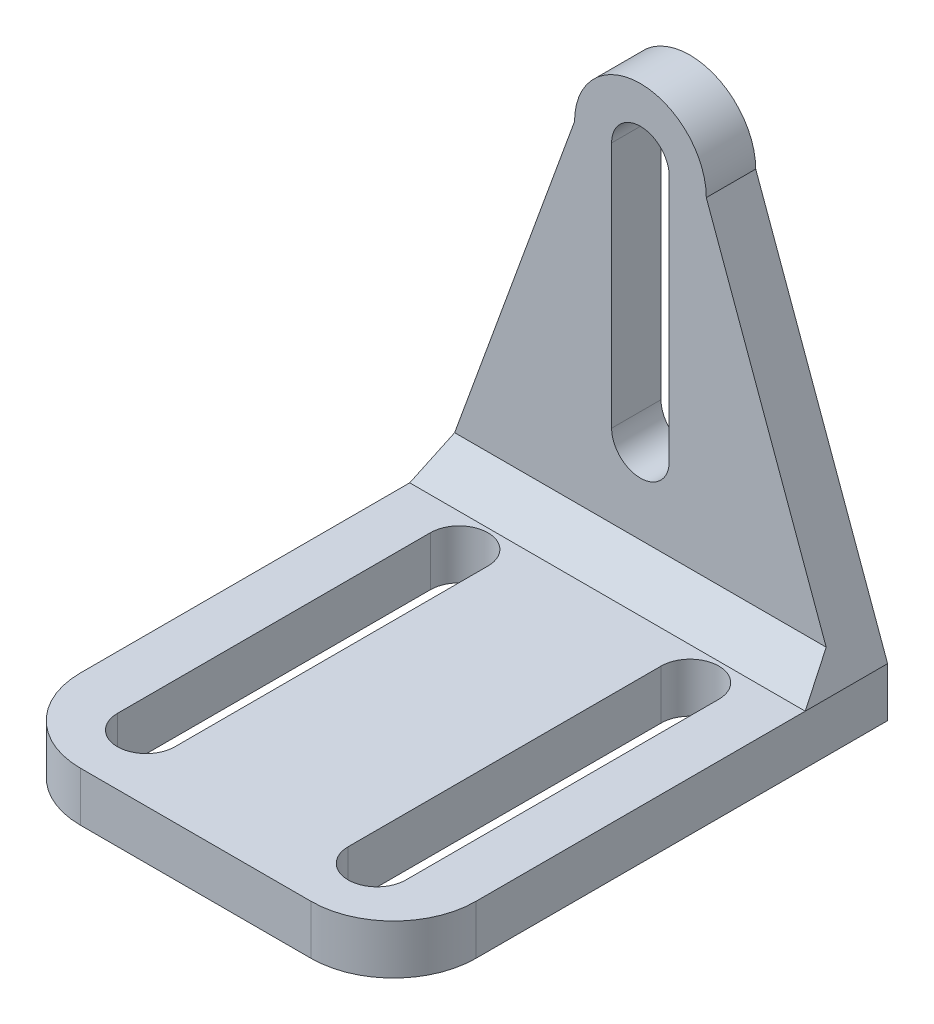
SolidWorks part; units mm, degrees
ref_plane "前视基准面" through (0, 0, 0) normal (0, 0, 1) x (1, 0, 0)
ref_plane "上视基准面" through (0, 0, 0) normal (0, 1, 0) x (1, 0, 0)
ref_plane "右视基准面" through (0, 0, 0) normal (1, 0, 0) x (0, 0, -1)
sketch "草图1" plane through (0, 0, 0) normal (0, 0, 1) x (1, 0, 0)
  line L0 (-4, 0) -> (-12.0073, -22)
  line L1 (12.0073, -22) -> (-12.0073, -22)
  line L2 (12.0073, -22) -> (4, 0)
  line L3 (0, 0) -> (0, -25) construction
  line L4 (-12.0073, -25) -> (12.0073, -25)
  line L5 (12.0073, -22) -> (12.0073, -25)
  line L6 (-12.0073, -25) -> (-12.0073, -22)
  line L7 (1.75, 0) -> (1.75, -15)
  line L8 (-1.75, 0) -> (-1.75, -15)
  circle A0 centre (0, 0) radius 1.75
  circle A1 centre (0, 0) radius 4
  circle A2 centre (0, -15) radius 1.75
  point P10 (0, -25)
  point P13 (0, -22)
  dimension "D1" = 3.5
  dimension "D2" = 8
  dimension "D6" = 3.5
  dimension "D3" = 20
  dimension "D4" = 3
  dimension "D5" = 22
  dimension "D7" = 15
extrude "凸台-拉伸1" add sketch "草图1" along normal blind 3 contours L3 A1 L0 L1 | A1 L3 L1 L2 | A0 A1 region at (-3.6673, -2.294, 0) region at (0, 3.8897, 0)
extrude "凸台-拉伸2" add sketch "草图1<3>" along normal blind 30 contours L3 L1 L6 L4 | L1 L3 L4 L5 region at (-6.0037, -23.5, 0) region at (6.0037, -23.5, 0)
sketch "草图1<3>" plane through (0, 0, 0) normal (0, 0, 1) x (1, 0, 0) same geometry as "草图1"
sketch "草图2" plane through (0, -22, 0) normal (0, 1, 0) x (1, 0, 0)
  line L0 (-7.0073, -3) -> (-7.0073, -30) construction
  line L1 (7.0073, -30) -> (7.0073, -3) construction
  line L2 (-5.2573, -7) -> (-5.2573, -26)
  line L3 (-8.7573, -7) -> (-8.7573, -26)
  line L4 (12.0073, -30) -> (12.0073, -3)
  line L5 (12.0073, -3) -> (-12.0073, -3)
  line L6 (-12.0073, -3) -> (-12.0073, -30)
  line L7 (-12.0073, -30) -> (12.0073, -30)
  line L8 (12.0073, -30) -> (12.0073, -3)
  line L9 (12.0073, -3) -> (-12.0073, -3)
  line L10 (-12.0073, -3) -> (-12.0073, -30)
  line L11 (-12.0073, -30) -> (12.0073, -30)
  line L12 (5.2573, -7) -> (5.2573, -26)
  line L13 (8.7573, -26) -> (8.7573, -7)
  circle A0 centre (-7.0073, -7) radius 1.75
  circle A1 centre (-7.0073, -26) radius 1.75
  circle A2 centre (7.0073, -7) radius 1.75
  circle A3 centre (7.0073, -26) radius 1.75
  dimension "D4" = 3.5
  dimension "D5" = 3.5
  dimension "D6" = 3.5
  dimension "D7" = 3.5
  dimension "D8" = 4
  dimension "D9" = 4
  dimension "D10" = 4
  dimension "D11" = 4
  dimension "D2" = 5
  dimension "D3" = 5
  dimension "D1" = 0
extrude "切除-拉伸1" cut sketch "草图2" against normal blind 15 contours A0 | A1 L2 A0 L3 | A1 | A3 | A3 L13 A2 L12 | A2 region at (-7.0073, -22, 7) region at (-7.0073, -22, 16.5) region at (-7.0073, -22, 26) region at (7.0073, -22, 16.5) region at (7.0073, -22, 7) region at (7.0073, -22, 26)
fillet "圆角1" radius 5 2 edges at (-12.0073, -23.5, 30) (12.0073, -23.5, 30)
chamfer "倒角1" distance 2 angle 45 1 edges at (0, -22, 3)
